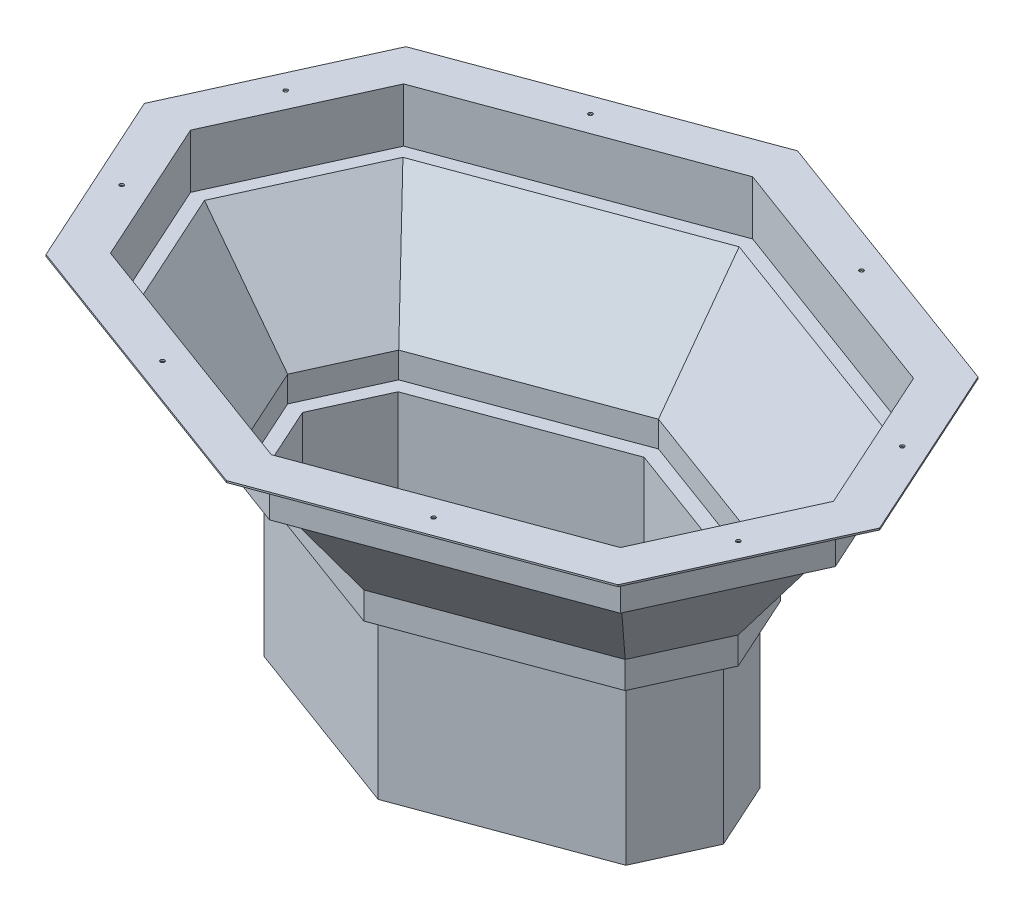
SolidWorks part; units mm, degrees
material "6061-T6 (SS)"
ref_plane "Front Plane" through (0, 0, 0) normal (0, 0, 1) x (1, 0, 0)
ref_plane "Top Plane" through (0, 0, 0) normal (0, 1, 0) x (1, 0, 0)
ref_plane "Right Plane" through (0, 0, 0) normal (1, 0, 0) x (0, 0, -1)
sketch "Sketch1" plane through (0, 0, 0) normal (0, 1, 0) x (1, 0, 0)
  line L0 (0, 0) -> (0, 457.2) construction
  line L1 (-609.6, 0) -> (-483.0506, 278.8894)
  line L2 (-609.6, 0) -> (0, 0) construction
  line L3 (483.0506, -278.8894) -> (-483.0506, -278.8894) construction
  line L4 (483.0506, -278.8894) -> (483.0506, 278.8894) construction
  line L5 (483.0506, 278.8894) -> (-483.0506, 278.8894) construction
  line L6 (-483.0506, -278.8894) -> (-483.0506, 278.8894) construction
  line L7 (483.0506, -278.8894) -> (-483.0506, 278.8894) construction
  line L8 (483.0506, 278.8894) -> (-483.0506, -278.8894) construction
  line L9 (-483.0506, 278.8894) -> (0, 457.2)
  line L10 (0, 457.2) -> (483.0506, 278.8894)
  line L11 (483.0506, 278.8894) -> (609.6, 0)
  line L12 (609.6, 0) -> (483.0506, -278.8894)
  line L13 (483.0506, -278.8894) -> (0, -457.2)
  line L14 (0, -457.2) -> (-483.0506, -278.8894)
  line L15 (-609.6, 0) -> (-483.0506, -278.8894)
  ellipse E0 centre (0, 0) end of major axis (-609.6, 0) minor radius 457.2 construction
  dimension "D1" = 609.6
  dimension "D2" = 457.2
  dimension "D3" = 30
extrude "Boss-Extrude1" add sketch "Sketch1" against normal blind 101.6
sketch "Sketch3" plane through (0, -101.6, 0) normal (0, -1, 0) x (1, 0, 0)
  line L0 (-464.3036, -258.7343) -> (0, -430.1247)
  line L1 (0, -430.1247) -> (464.3036, -258.7343)
  line L2 (464.3036, -258.7343) -> (581.7074, 0)
  line L3 (581.7074, 0) -> (464.3036, 258.7343)
  line L4 (464.3036, 258.7343) -> (0, 430.1247)
  line L5 (0, 430.1247) -> (-464.3036, 258.7343)
  line L6 (-464.3036, 258.7343) -> (-581.7074, 0)
  line L7 (-581.7074, 0) -> (-464.3036, -258.7343)
  line L8 (-483.0506, -278.8894) -> (0, -457.2)
  line L9 (0, -457.2) -> (483.0506, -278.8894)
  line L10 (483.0506, -278.8894) -> (609.6, 0)
  line L11 (609.6, 0) -> (483.0506, 278.8894)
  line L12 (483.0506, 278.8894) -> (0, 457.2)
  line L13 (0, 457.2) -> (-483.0506, 278.8894)
  line L14 (-483.0506, 278.8894) -> (-609.6, 0)
  line L15 (-609.6, 0) -> (-483.0506, -278.8894)
  line L16 (-483.0506, -278.8894) -> (0, -457.2) construction
  line L17 (0, -457.2) -> (483.0506, -278.8894) construction
  line L18 (483.0506, -278.8894) -> (609.6, 0) construction
  line L19 (609.6, 0) -> (483.0506, 278.8894) construction
  line L20 (483.0506, 278.8894) -> (0, 457.2) construction
  line L21 (0, 457.2) -> (-483.0506, 278.8894) construction
  line L22 (-483.0506, 278.8894) -> (-609.6, 0) construction
  line L23 (-609.6, 0) -> (-483.0506, -278.8894) construction
  dimension "D1" = 0
  dimension "D2" = 25.4
ref_plane "Plane1" through (0, -304.8, 0) normal (0, -1, 0) x (-1, 0, 0)
sketch "Sketch2" plane through (0, -304.8, 0) normal (0, -1, 0) x (-1, 0, 0)
  line L0 (0, 279.4925) -> (-360.0052, 146.6021)
  line L1 (-360.0052, 146.6021) -> (-426.5277, 0)
  line L2 (-426.5277, 0) -> (-360.0052, -146.6021)
  line L3 (-360.0052, -146.6021) -> (0, -279.4925)
  line L4 (0, -279.4925) -> (360.0052, -146.6021)
  line L5 (360.0052, -146.6021) -> (426.5277, 0)
  line L6 (426.5277, 0) -> (360.0052, 146.6021)
  line L7 (360.0052, 146.6021) -> (0, 279.4925)
  line L8 (483.0506, 278.8894) -> (0, 457.2)
  line L9 (609.6, 0) -> (483.0506, 278.8894)
  line L10 (483.0506, -278.8894) -> (609.6, 0)
  line L11 (0, -457.2) -> (483.0506, -278.8894)
  line L12 (-483.0506, -278.8894) -> (0, -457.2)
  line L13 (-609.6, 0) -> (-483.0506, -278.8894)
  line L14 (-483.0506, 278.8894) -> (-609.6, 0)
  line L15 (0, 457.2) -> (-483.0506, 278.8894)
  line L16 (483.0506, 278.8894) -> (0, 457.2) construction
  line L17 (609.6, 0) -> (483.0506, 278.8894) construction
  line L18 (483.0506, -278.8894) -> (609.6, 0) construction
  line L19 (0, -457.2) -> (483.0506, -278.8894) construction
  line L20 (-483.0506, -278.8894) -> (0, -457.2) construction
  line L21 (-609.6, 0) -> (-483.0506, -278.8894) construction
  line L22 (-483.0506, 278.8894) -> (-609.6, 0) construction
  line L23 (0, 457.2) -> (-483.0506, 278.8894) construction
  dimension "D2" = 177.7075
  dimension "D3" = 166.712
  dimension "D4" = 166.712
  dimension "D5" = 166.712
  dimension "D6" = 166.712
  dimension "D7" = 166.712
  dimension "D8" = 166.712
  dimension "D9" = 166.712
  dimension "D1" = 0
loft "Loft1" add profiles "Sketch3", "Sketch2" connector at (-464.3036, -101.6, 258.7343) connector at (-360.0052, -304.8, 146.6021)
sketch "Sketch4" plane through (0, -304.8, 0) normal (0, -1, 0) x (1, 0, 0)
  line L8 (0, -279.4925) -> (360.0052, -146.6021)
  line L9 (0, -279.4925) -> (360.0052, -146.6021)
  line L10 (360.0052, -146.6021) -> (426.5277, 0)
  line L11 (360.0052, -146.6021) -> (426.5277, 0)
  line L12 (426.5277, 0) -> (360.0052, 146.6021)
  line L13 (426.5277, 0) -> (360.0052, 146.6021)
  line L14 (360.0052, 146.6021) -> (0, 279.4925)
  line L15 (360.0052, 146.6021) -> (0, 279.4925)
  line L16 (0, 279.4925) -> (-360.0052, 146.6021)
  line L17 (0, 279.4925) -> (-360.0052, 146.6021)
  line L18 (-360.0052, 146.6021) -> (-426.5277, 0)
  line L19 (-360.0052, 146.6021) -> (-426.5277, 0)
  line L20 (-426.5277, 0) -> (-360.0052, -146.6021)
  line L21 (-426.5277, 0) -> (-360.0052, -146.6021)
  line L22 (-360.0052, -146.6021) -> (0, -279.4925)
  line L23 (-360.0052, -146.6021) -> (0, -279.4925)
  dimension "D1" = 0
extrude "Boss-Extrude2" add sketch "Sketch4" along normal blind 50.8
sketch "Sketch5" plane through (0, 0, 0) normal (0, 1, 0) x (1, 0, 0)
  line L0 (0, 538.4258) -> (-539.2916, 339.3547)
  line L1 (-539.2916, 339.3547) -> (-693.2779, 0)
  line L2 (-693.2779, 0) -> (-539.2916, -339.3547)
  line L3 (-539.2916, -339.3547) -> (0, -538.4258)
  line L4 (0, -538.4258) -> (539.2916, -339.3547)
  line L5 (539.2916, -339.3547) -> (693.2779, 0)
  line L6 (693.2779, 0) -> (539.2916, 339.3547)
  line L7 (539.2916, 339.3547) -> (0, 538.4258)
  line L8 (0, 457.2) -> (-483.0506, 278.8894)
  line L9 (-483.0506, 278.8894) -> (-609.6, 0)
  line L10 (-609.6, 0) -> (-483.0506, -278.8894)
  line L11 (-483.0506, -278.8894) -> (0, -457.2)
  line L12 (0, -457.2) -> (483.0506, -278.8894)
  line L13 (483.0506, -278.8894) -> (609.6, 0)
  line L14 (609.6, 0) -> (483.0506, 278.8894)
  line L15 (483.0506, 278.8894) -> (0, 457.2)
  line L16 (0, 457.2) -> (-483.0506, 278.8894) construction
  line L17 (-483.0506, 278.8894) -> (-609.6, 0) construction
  line L18 (-609.6, 0) -> (-483.0506, -278.8894) construction
  line L19 (-483.0506, -278.8894) -> (0, -457.2) construction
  line L20 (0, -457.2) -> (483.0506, -278.8894) construction
  line L21 (483.0506, -278.8894) -> (609.6, 0) construction
  line L22 (609.6, 0) -> (483.0506, 278.8894) construction
  line L23 (483.0506, 278.8894) -> (0, 457.2) construction
  dimension "D1" = 0
  dimension "D2" = 76.2
extrude "Boss-Extrude3" add sketch "Sketch5" along normal blind 3.175
sketch "Sketch6" plane through (0, -355.6, 0) normal (0, -1, 0) x (1, 0, 0)
  line L0 (0, 252.4172) -> (-341.2582, 126.447)
  line L1 (-341.2582, 126.447) -> (-398.6351, 0)
  line L2 (-398.6351, 0) -> (-341.2582, -126.447)
  line L3 (-341.2582, -126.447) -> (0, -252.4172)
  line L4 (0, -252.4172) -> (341.2582, -126.447)
  line L5 (341.2582, -126.447) -> (398.6351, 0)
  line L6 (398.6351, 0) -> (341.2582, 126.447)
  line L7 (341.2582, 126.447) -> (0, 252.4172)
  line L8 (360.0052, -146.6021) -> (426.5277, 0)
  line L9 (426.5277, 0) -> (360.0052, 146.6021)
  line L10 (360.0052, 146.6021) -> (0, 279.4925)
  line L11 (0, 279.4925) -> (-360.0052, 146.6021)
  line L12 (-360.0052, 146.6021) -> (-426.5277, 0)
  line L13 (-426.5277, 0) -> (-360.0052, -146.6021)
  line L14 (-360.0052, -146.6021) -> (0, -279.4925)
  line L15 (0, -279.4925) -> (360.0052, -146.6021)
  line L16 (360.0052, -146.6021) -> (426.5277, 0) construction
  line L17 (426.5277, 0) -> (360.0052, 146.6021) construction
  line L18 (360.0052, 146.6021) -> (0, 279.4925) construction
  line L19 (0, 279.4925) -> (-360.0052, 146.6021) construction
  line L20 (-360.0052, 146.6021) -> (-426.5277, 0) construction
  line L21 (-426.5277, 0) -> (-360.0052, -146.6021) construction
  line L22 (-360.0052, -146.6021) -> (0, -279.4925) construction
  line L23 (0, -279.4925) -> (360.0052, -146.6021) construction
  dimension "D1" = 0
  dimension "D2" = 25.4
extrude "Boss-Extrude4" add sketch "Sketch6" along normal blind 304.8
shell "Shell2" thickness 3.175 removed face at (0, 3.175, 0)
sketch "Sketch7" [suppressed] plane through (0, 0, 0) normal (0, 1, 0) x (1, 0, 0)
  line L0 (-357.6619, 144.0827) -> (0, 276.108) construction
  line L1 (-423.0411, 0) -> (-357.6619, 144.0827) construction
  line L2 (-357.6619, -144.0827) -> (-423.0411, 0) construction
  line L3 (-357.6619, -144.0827) -> (0, -276.108) construction
  line L4 (0, -276.108) -> (357.6619, -144.0827) construction
  line L5 (357.6619, -144.0827) -> (423.0411, 0) construction
  line L6 (357.6619, 144.0827) -> (423.0411, 0) construction
  line L7 (357.6619, 144.0827) -> (0, 276.108) construction
  line L8 (-357.6619, 144.0827) -> (0, 276.108) construction
  line L9 (-423.0411, 0) -> (-357.6619, 144.0827) construction
  line L10 (-357.6619, -144.0827) -> (-423.0411, 0) construction
  line L11 (-357.6619, -144.0827) -> (0, -276.108) construction
  line L12 (0, -276.108) -> (357.6619, -144.0827) construction
  line L13 (357.6619, -144.0827) -> (423.0411, 0) construction
  line L14 (357.6619, 144.0827) -> (423.0411, 0) construction
  line L15 (357.6619, 144.0827) -> (0, 276.108) construction
sketch "Sketch8" plane through (0, 3.175, 0) normal (0, 1, 0) x (1, 0, 0)
  line L0 (511.1711, 309.122) -> (0, 497.8129) construction
  line L1 (0, 497.8129) -> (-511.1711, 309.122) construction
  line L2 (-511.1711, 309.122) -> (-651.4389, 0) construction
  line L3 (-651.4389, 0) -> (-511.1711, -309.122) construction
  line L4 (-511.1711, -309.122) -> (0, -497.8129) construction
  line L5 (0, -497.8129) -> (511.1711, -309.122) construction
  line L6 (511.1711, -309.122) -> (651.4389, 0) construction
  line L7 (651.4389, 0) -> (511.1711, 309.122) construction
  line L8 (539.2916, 339.3547) -> (0, 538.4258)
  line L9 (0, 538.4258) -> (-539.2916, 339.3547)
  line L10 (-539.2916, 339.3547) -> (-693.2779, 0)
  line L11 (-693.2779, 0) -> (-539.2916, -339.3547)
  line L12 (-539.2916, -339.3547) -> (0, -538.4258)
  line L13 (0, -538.4258) -> (539.2916, -339.3547)
  line L14 (539.2916, -339.3547) -> (693.2779, 0)
  line L15 (693.2779, 0) -> (539.2916, 339.3547)
  line L16 (539.2916, 339.3547) -> (0, 538.4258) construction
  line L17 (0, 538.4258) -> (-539.2916, 339.3547) construction
  line L18 (-539.2916, 339.3547) -> (-693.2779, 0) construction
  line L19 (-693.2779, 0) -> (-539.2916, -339.3547) construction
  line L20 (-539.2916, -339.3547) -> (0, -538.4258) construction
  line L21 (0, -538.4258) -> (539.2916, -339.3547) construction
  line L22 (539.2916, -339.3547) -> (693.2779, 0) construction
  line L23 (693.2779, 0) -> (539.2916, 339.3547) construction
  circle A0 centre (-255.5855, 403.4675) radius 3.81
  circle A1 centre (255.5855, 403.4675) radius 3.81
  circle A2 centre (581.305, 154.561) radius 3.81
  circle A3 centre (581.305, -154.561) radius 3.81
  circle A4 centre (255.5855, -403.4675) radius 3.81
  circle A5 centre (-255.5855, -403.4675) radius 3.81
  circle A6 centre (-581.305, -154.561) radius 3.81
  circle A7 centre (-581.305, 154.561) radius 3.81
  dimension "D3" = 7.62
  dimension "D1" = 0
  dimension "D2" = 38.1
extrude "Cut-Extrude1" cut sketch "Sketch8" against normal up to next
